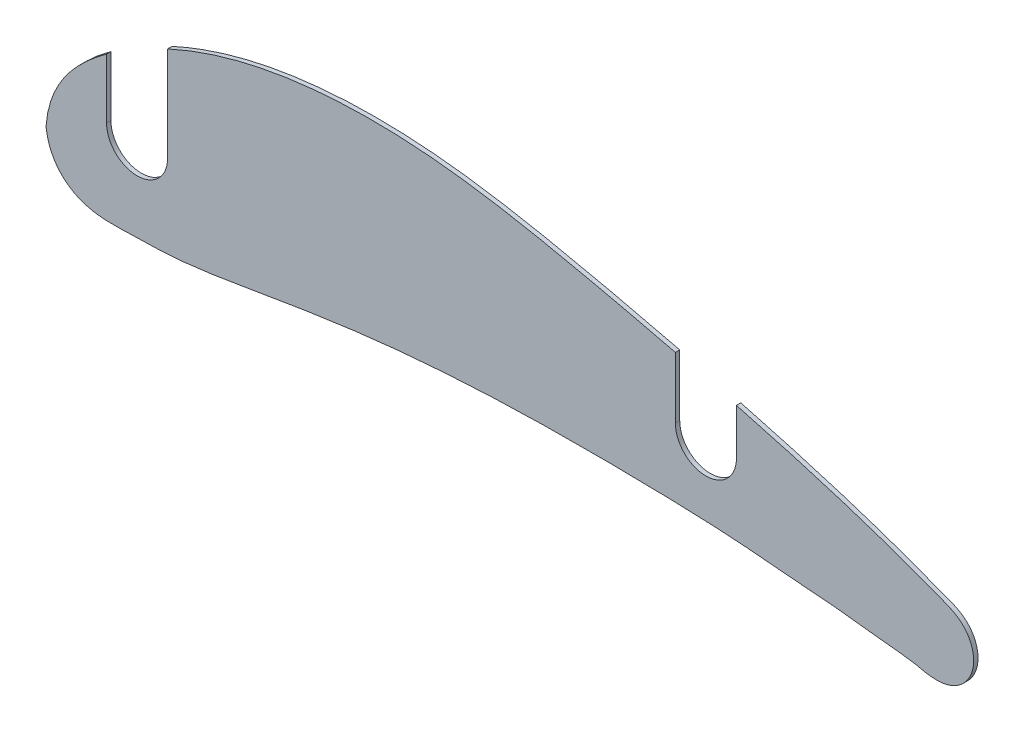
SolidWorks part; units mm, degrees
material "Balsa"
ref_plane "Front Plane" through (0, 0, 0) normal (0, 0, 1) x (1, 0, 0)
ref_plane "Top Plane" through (0, 0, 0) normal (0, 1, 0) x (1, 0, 0)
ref_plane "Right Plane" through (0, 0, 0) normal (1, 0, 0) x (0, 0, -1)
sketch "Sketch1" plane through (0, 0, 0) normal (0, 0, 1) x (1, 0, 0)
  spline S0 degree 3 poles (0.0006, 0.0001) (0.8106, 7.3592) (8.6491, 17.8566) (26.2867, 29.9752) (52.1111, 42.0692) (89.5976, 49.2908) (131.4008, 47.8848) (173.2567, 40.0411) (217.9611, 29.613) (256.9521, 19.5289) (290.3598, 8.711) (301.2732, 4.3828) (314.8169, -0.5162) (309.8463, 0.0001) knots 0 0 0 0 0.060864 0.113688 0.188609 0.312909 0.448482 0.557612 0.691544 0.852438 0.929756 0.976058 1 1 1 1
  spline S1 degree 3 poles (309.8463, 0.0001) (303.9568, 1.471) (293.9895, 2.094) (276.264, 4.5144) (260.8463, 5.4274) (235.8588, 7.8703) (205.1014, 8.8381) (157.7186, 9.0307) (110.4973, 6.1815) (66.5062, -0.5867) (36.4547, -6.0985) (15.3166, -6.1891) (1.2307, -6.9241) (0.0006, 0.0001) knots 0 0 0 0 0.057787 0.095275 0.171021 0.205339 0.335319 0.464904 0.658702 0.785512 0.893517 0.943092 1 1 1 1
extrude "Boss-Extrude1" add sketch "Sketch1" along normal blind 1.5875
sketch "Sketch2" plane through (0, 0, 1.5875) normal (0, 0, 1) x (1, 0, 0)
  circle A0 centre (20.32, 10.16) radius 6.5
  circle A1 centre (227.2963, 19.0501) radius 3
  circle A2 centre (20.32, 10.16) radius 5.75
  circle A3 centre (20.32, 10.16) radius 8
  circle A4 centre (227.2963, 19.0501) radius 4.5
  circle A5 centre (227.2963, 19.0501) radius 2.5
  dimension "D2" = 13
  dimension "D3" = 6
  dimension "D6" = 20.32
  dimension "D7" = 1.5
  dimension "D8" = 11.5
  dimension "D9" = 5
  dimension "D10" = 1.5
  dimension "D1" = 82.55
  dimension "D4" = 19.05
  dimension "D5" = 10.16
extrude "Cut-Extrude1" cut sketch "Sketch2" against normal blind 4 contours A5 | A2 region at (20.32, 10.16, 1.5875) region at (227.2963, 19.0501, 1.5875)
sketch "Sketch3" plane through (0, 0, 1.5875) normal (0, 0, 1) x (1, 0, 0)
  circle A0 centre (20.32, 10.16) radius 5.75
  circle A1 centre (227.2963, 19.0501) radius 2.5
  spline S4 degree 3 poles (-537.5821, 2953.3046) (-362.5867, 1968.3024) (-187.5913, 983.3001) (-12.5202, -2.1281) (-12.4462, -2.5545) (-12.176, -3.8198) (-11.9472, -4.6494) (-11.3848, -6.2785) (-11.0505, -7.0797) (-10.2706, -8.6419) (-9.8324, -9.3883) (-8.861, -10.8126) (-8.3277, -11.4905) (-7.4547, -12.4548) (-7.1506, -12.7683) (-6.5217, -13.3733) (-6.1984, -13.6633) (-5.2034, -14.4972) (-4.5063, -15.0051) (-3.4124, -15.698) (-3.0397, -15.9175) (-2.2783, -16.3337) (-1.8884, -16.531) (0.0848, -17.4542) (1.7227, -17.9852) (4.2479, -18.5428) (5.101, -18.6886) (6.8269, -18.9121) (7.6891, -18.9885) (10.2729, -19.1376) (11.9923, -19.129) (14.5697, -19.0646) (15.4287, -19.0354) (17.1468, -18.9865) (18.006, -18.9648) (22.3019, -18.8623) (25.7393, -18.8009) (30.8907, -18.5548) (32.6071, -18.445) (36.0379, -18.1654) (37.7526, -17.9976) (46.3222, -17.046) (53.1404, -15.9299) (63.3607, -14.1884) (66.7665, -13.5989) (73.5825, -12.4617) (76.9921, -11.9088) (87.2279, -10.3137) (94.0606, -9.3352) (107.7529, -7.6313) (114.6131, -6.9129) (128.3595, -5.7224) (135.2455, -5.2485) (149.0401, -4.5139) (155.9486, -4.2533) (166.3263, -4.0025) (169.789, -3.9425) (176.7136, -3.8642) (187.0965, -3.8094) (197.4692, -3.9166) (211.2933, -4.1577) (218.2024, -4.3251) (232.0057, -4.8961) (238.8998, -5.3016) (249.2232, -6.1931) (252.662, -6.5269) (259.5451, -7.1075) (262.9889, -7.3618) (269.8748, -7.8975) (273.3169, -8.1788) (278.4736, -8.7044) (280.1911, -8.9011) (283.6248, -9.3158) (285.3412, -9.5311) (288.7752, -9.9413) (290.493, -10.1333) (293.9309, -10.4809) (295.6507, -10.6423) (299.0876, -11.0065) (300.8047, -11.2088) (303.3742, -11.6118) (304.2297, -11.763) (305.5105, -12.0268) (305.9371, -12.1209) (335.3871, -19.1372) (362.2719, -60.0398) (582.5295, 2971.454) knots -9.029911 -9.029911 -9.029911 -9.029911 0.003906 0.003906 0.007813 0.007813 0.015625 0.015625 0.023438 0.023438 0.03125 0.03125 0.039063 0.039063 0.042969 0.042969 0.046875 0.046875 0.054688 0.054688 0.058594 0.058594 0.0625 0.0625 0.078125 0.078125 0.085938 0.085938 0.09375 0.09375 0.109375 0.109375 0.117188 0.117188 0.125 0.125 0.15625 0.15625 0.171875 0.171875 0.1875 0.1875 0.25 0.25 0.28125 0.28125 0.3125 0.3125 0.375 0.375 0.4375 0.4375 0.5 0.5 0.5625 0.5625 0.59375 0.59375 0.625 0.6875 0.6875 0.75 0.75 0.8125 0.8125 0.84375 0.84375 0.875 0.875 0.90625 0.90625 0.921875 0.921875 0.9375 0.9375 0.953125 0.953125 0.96875 0.96875 0.984375 0.984375 0.992188 0.992188 0.996094 0.996094 1.262177 1.262177 1.262177 1.262177 only from (-12.8229, -0.4244) to (307.6407, -12.5391)
  spline S5 degree 3 poles (-30.8299, -2991.3817) (252.0246, 34.8902) (278.8555, -10.0807) (309.7432, -12.7424) (310.2709, -12.7759) (311.3268, -12.8029) (311.854, -12.7961) (312.9063, -12.7287) (313.4338, -12.6676) (314.9872, -12.3972) (315.988, -12.1026) (317.4337, -11.4794) (317.9089, -11.2395) (318.8157, -10.7098) (319.6838, -10.1289) (320.4759, -9.4471) (321.2289, -8.7136) (321.5865, -8.3194) (322.5699, -7.0911) (323.1187, -6.2025) (323.7782, -4.7628) (323.9683, -4.2689) (324.2836, -3.2709) (324.4101, -2.7643) (324.6008, -1.736) (324.6652, -1.2125) (324.7285, -0.1569) (324.726, 0.8922) (324.5965, 1.9288) (324.4029, 2.9591) (324.2728, 3.4747) (323.7925, 4.9788) (323.3556, 5.9274) (322.5268, 7.2699) (322.2202, 7.7046) (321.5647, 8.5239) (321.2141, 8.9115) (320.4688, 9.6443) (320.074, 9.9894) (319.2406, 10.6374) (318.8058, 10.937) (317.4727, 11.7599) (316.5372, 12.2119) (314.6262, 13.0336) (313.6522, 13.4065) (311.697, 14.1371) (310.7161, 14.4939) (308.7579, 15.2168) (307.7794, 15.5801) (304.8459, 16.6752) (302.8934, 17.4143) (298.9854, 18.8838) (297.0281, 19.6095) (293.0959, 21.0105) (291.1228, 21.6913) (287.1674, 23.027) (285.1851, 23.6817) (279.2276, 25.616) (275.2421, 26.8663) (267.2584, 29.3011) (263.2585, 30.4844) (251.2359, 33.938) (243.1898, 36.1098) (231.0876, 39.2285) (227.0482, 40.2454) (218.9619, 42.248) (214.9155, 43.2353) (202.7668, 46.1582) (194.6542, 48.0498) (182.454, 50.7556) (178.3821, 51.6355) (170.2257, 53.3429) (166.1416, 54.1717) (157.9516, 55.7375) (151.7928, 56.8428) (145.598, 57.7968) (141.4589, 58.394) (139.384, 58.6732) (129.01, 59.9562) (120.6949, 60.6191) (108.1942, 60.9702) (104.0226, 60.98) (97.7575, 60.8192) (95.6678, 60.7364) (91.4859, 60.5096) (89.398, 60.3659) (79.0016, 59.4934) (70.7948, 58.305) (54.6421, 54.769) (46.6965, 52.4202) (37.9375, 48.979) (36.9667, 48.5856) (35.0302, 47.7767) (34.0635, 47.3607) (31.1797, 46.0826) (29.2785, 45.1906) (23.6392, 42.3949) (19.964, 40.3738) (14.5845, 37.0929) (12.8113, 35.9519) (9.3552, 33.571) (7.6711, 32.3308) (4.4084, 29.7311) (2.8297, 28.3718) (-0.2058, 25.5152) (-1.6628, 24.0183) (-3.3771, 22.0263) (-3.7146, 21.6218) (-4.3781, 20.7998) (-4.7047, 20.3815) (-5.6607, 19.1122) (-6.2653, 18.2488) (-7.9744, 15.603) (-8.9741, 13.7652) (-10.2375, 10.8836) (-10.6193, 9.9022) (-11.129, 8.3969) (-11.2886, 7.8885) (-11.5839, 6.8689) (-11.9916, 5.3328) (-12.2943, 3.7769) (-12.5275, 2.208) (-12.591, 1.6823) (-122.1238, -993.3635) (-231.5987, -1987.8827) (-341.0735, -2982.4019) knots -0.22153 -0.22153 -0.22153 -0.22153 0.003906 0.003906 0.007812 0.007812 0.011719 0.011719 0.015625 0.015625 0.023437 0.023437 0.027344 0.027344 0.03125 0.035156 0.035156 0.039062 0.039062 0.046875 0.046875 0.050781 0.050781 0.054687 0.054687 0.058594 0.058594 0.0625 0.066406 0.066406 0.070312 0.070312 0.078125 0.078125 0.082031 0.082031 0.085937 0.085937 0.089844 0.089844 0.09375 0.09375 0.101562 0.101562 0.109375 0.109375 0.117187 0.117187 0.125 0.125 0.140625 0.140625 0.15625 0.15625 0.171875 0.171875 0.1875 0.1875 0.21875 0.21875 0.25 0.25 0.3125 0.3125 0.34375 0.34375 0.375 0.375 0.4375 0.4375 0.46875 0.46875 0.5 0.5 0.53125 0.546875 0.546875 0.5625 0.5625 0.625 0.625 0.65625 0.65625 0.671875 0.671875 0.6875 0.6875 0.75 0.75 0.8125 0.8125 0.820312 0.820312 0.828125 0.828125 0.84375 0.84375 0.875 0.875 0.890625 0.890625 0.90625 0.90625 0.921875 0.921875 0.9375 0.9375 0.941406 0.941406 0.945312 0.945312 0.953125 0.953125 0.96875 0.96875 0.976562 0.976562 0.980469 0.980469 0.984375 0.992187 0.992187 0.996094 0.996094 8.372097 8.372097 8.372097 8.372097 only from (307.6407, -12.5391) to (-12.8229, -0.4244)
  spline S6 degree 3 poles (-12.8229, -0.4244) (-12.7472, -0.8503) (-12.6715, -1.2762) (-12.5202, -2.1281) (-12.4462, -2.5545) (-12.176, -3.8198) (-11.9472, -4.6494) (-11.3848, -6.2785) (-11.0505, -7.0797) (-10.2706, -8.6419) (-9.8324, -9.3883) (-8.861, -10.8126) (-8.3277, -11.4905) (-7.4547, -12.4548) (-7.1506, -12.7683) (-6.5217, -13.3733) (-6.1984, -13.6633) (-5.2034, -14.4972) (-4.5063, -15.0051) (-3.4124, -15.698) (-3.0397, -15.9175) (-2.2783, -16.3337) (-1.8884, -16.531) (0.0848, -17.4542) (1.7227, -17.9852) (4.2479, -18.5428) (5.101, -18.6886) (6.8269, -18.9121) (7.6891, -18.9885) (10.2729, -19.1376) (11.9923, -19.129) (14.5697, -19.0646) (15.4287, -19.0354) (17.1468, -18.9865) (18.006, -18.9648) (22.3019, -18.8623) (25.7393, -18.8009) (30.8907, -18.5548) (32.6071, -18.445) (36.0379, -18.1654) (37.7526, -17.9976) (46.3222, -17.046) (53.1404, -15.9299) (63.3607, -14.1884) (66.7665, -13.5989) (73.5825, -12.4617) (76.9921, -11.9088) (87.2279, -10.3137) (94.0606, -9.3352) (107.7529, -7.6313) (114.6131, -6.9129) (128.3595, -5.7224) (135.2455, -5.2485) (149.0401, -4.5139) (155.9486, -4.2533) (166.3263, -4.0025) (169.789, -3.9425) (176.7136, -3.8642) (187.0965, -3.8094) (197.4692, -3.9166) (211.2933, -4.1577) (218.2024, -4.3251) (232.0057, -4.8961) (238.8998, -5.3016) (249.2232, -6.1931) (252.662, -6.5269) (259.5451, -7.1075) (262.9889, -7.3618) (269.8748, -7.8975) (273.3169, -8.1788) (278.4736, -8.7044) (280.1911, -8.9011) (283.6248, -9.3158) (285.3412, -9.5311) (288.7752, -9.9413) (290.493, -10.1333) (293.9309, -10.4809) (295.6507, -10.6423) (299.0876, -11.0065) (300.8047, -11.2088) (303.3742, -11.6118) (304.2297, -11.763) (305.5105, -12.0268) (305.9371, -12.1209) (306.7892, -12.3239) (307.2149, -12.4328) (307.6407, -12.5391) knots 0 0 0 0 0.003906 0.003906 0.007813 0.007813 0.015625 0.015625 0.023438 0.023438 0.03125 0.03125 0.039063 0.039063 0.042969 0.042969 0.046875 0.046875 0.054688 0.054688 0.058594 0.058594 0.0625 0.0625 0.078125 0.078125 0.085938 0.085938 0.09375 0.09375 0.109375 0.109375 0.117188 0.117188 0.125 0.125 0.15625 0.15625 0.171875 0.171875 0.1875 0.1875 0.25 0.25 0.28125 0.28125 0.3125 0.3125 0.375 0.375 0.4375 0.4375 0.5 0.5 0.5625 0.5625 0.59375 0.59375 0.625 0.6875 0.6875 0.75 0.75 0.8125 0.8125 0.84375 0.84375 0.875 0.875 0.90625 0.90625 0.921875 0.921875 0.9375 0.9375 0.953125 0.953125 0.96875 0.96875 0.984375 0.984375 0.992188 0.992188 0.996094 0.996094 1 1 1 1
  spline S7 degree 3 poles (307.6407, -12.5391) (308.166, -12.5937) (308.691, -12.6517) (309.7432, -12.7424) (310.2709, -12.7759) (311.3268, -12.8029) (311.854, -12.7961) (312.9063, -12.7287) (313.4338, -12.6676) (314.9872, -12.3972) (315.988, -12.1026) (317.4337, -11.4794) (317.9089, -11.2395) (318.8157, -10.7098) (319.6838, -10.1289) (320.4759, -9.4471) (321.2289, -8.7136) (321.5865, -8.3194) (322.5699, -7.0911) (323.1187, -6.2025) (323.7782, -4.7628) (323.9683, -4.2689) (324.2836, -3.2709) (324.4101, -2.7643) (324.6008, -1.736) (324.6652, -1.2125) (324.7285, -0.1569) (324.726, 0.8922) (324.5965, 1.9288) (324.4029, 2.9591) (324.2728, 3.4747) (323.7925, 4.9788) (323.3556, 5.9274) (322.5268, 7.2699) (322.2202, 7.7046) (321.5647, 8.5239) (321.2141, 8.9115) (320.4688, 9.6443) (320.074, 9.9894) (319.2406, 10.6374) (318.8058, 10.937) (317.4727, 11.7599) (316.5372, 12.2119) (314.6262, 13.0336) (313.6522, 13.4065) (311.697, 14.1371) (310.7161, 14.4939) (308.7579, 15.2168) (307.7794, 15.5801) (304.8459, 16.6752) (302.8934, 17.4143) (298.9854, 18.8838) (297.0281, 19.6095) (293.0959, 21.0105) (291.1228, 21.6913) (287.1674, 23.027) (285.1851, 23.6817) (279.2276, 25.616) (275.2421, 26.8663) (267.2584, 29.3011) (263.2585, 30.4844) (251.2359, 33.938) (243.1898, 36.1098) (231.0876, 39.2285) (227.0482, 40.2454) (218.9619, 42.248) (214.9155, 43.2353) (202.7668, 46.1582) (194.6542, 48.0498) (182.454, 50.7556) (178.3821, 51.6355) (170.2257, 53.3429) (166.1416, 54.1717) (157.9516, 55.7375) (151.7928, 56.8428) (145.598, 57.7968) (141.4589, 58.394) (139.384, 58.6732) (129.01, 59.9562) (120.6949, 60.6191) (108.1942, 60.9702) (104.0226, 60.98) (97.7575, 60.8192) (95.6678, 60.7364) (91.4859, 60.5096) (89.398, 60.3659) (79.0016, 59.4934) (70.7948, 58.305) (54.6421, 54.769) (46.6965, 52.4202) (37.9375, 48.979) (36.9667, 48.5856) (35.0302, 47.7767) (34.0635, 47.3607) (31.1797, 46.0826) (29.2785, 45.1906) (23.6392, 42.3949) (19.964, 40.3738) (14.5845, 37.0929) (12.8113, 35.9519) (9.3552, 33.571) (7.6711, 32.3308) (4.4084, 29.7311) (2.8297, 28.3718) (-0.2058, 25.5152) (-1.6628, 24.0183) (-3.3771, 22.0263) (-3.7146, 21.6218) (-4.3781, 20.7998) (-4.7047, 20.3815) (-5.6607, 19.1122) (-6.2653, 18.2488) (-7.9744, 15.603) (-8.9741, 13.7652) (-10.2375, 10.8836) (-10.6193, 9.9022) (-11.129, 8.3969) (-11.2886, 7.8885) (-11.5839, 6.8689) (-11.9916, 5.3328) (-12.2943, 3.7769) (-12.5275, 2.208) (-12.591, 1.6823) (-12.7069, 0.629) (-12.7649, 0.1023) (-12.8229, -0.4244) knots 0 0 0 0 0.003906 0.003906 0.007812 0.007812 0.011719 0.011719 0.015625 0.015625 0.023437 0.023437 0.027344 0.027344 0.03125 0.035156 0.035156 0.039062 0.039062 0.046875 0.046875 0.050781 0.050781 0.054687 0.054687 0.058594 0.058594 0.0625 0.066406 0.066406 0.070312 0.070312 0.078125 0.078125 0.082031 0.082031 0.085937 0.085937 0.089844 0.089844 0.09375 0.09375 0.101562 0.101562 0.109375 0.109375 0.117187 0.117187 0.125 0.125 0.140625 0.140625 0.15625 0.15625 0.171875 0.171875 0.1875 0.1875 0.21875 0.21875 0.25 0.25 0.3125 0.3125 0.34375 0.34375 0.375 0.375 0.4375 0.4375 0.46875 0.46875 0.5 0.5 0.53125 0.546875 0.546875 0.5625 0.5625 0.625 0.625 0.65625 0.65625 0.671875 0.671875 0.6875 0.6875 0.75 0.75 0.8125 0.8125 0.820312 0.820312 0.828125 0.828125 0.84375 0.84375 0.875 0.875 0.890625 0.890625 0.90625 0.90625 0.921875 0.921875 0.9375 0.9375 0.941406 0.941406 0.945312 0.945312 0.953125 0.953125 0.96875 0.96875 0.976562 0.976562 0.980469 0.980469 0.984375 0.992187 0.992187 0.996094 0.996094 1 1 1 1
  dimension "D1" = 12.7
extrude "Boss-Extrude3" add sketch "Sketch3" against normal up to surface (1.5875 mm away) up to face at (224.7963, 19.0501, 0)
sketch "Sketch4" plane through (0, 0, 1.5875) normal (0, 0, 1) x (1, 0, 0)
  line L0 (9.2075, 11.7475) -> (9.2075, 65.1747)
  line L1 (31.4325, 65.1747) -> (31.4325, 11.7475)
  line L2 (9.2075, 65.1747) -> (31.4325, 65.1747)
  line L3 (216.1838, 62.4176) -> (216.1838, 20.6376)
  line L4 (238.4088, 20.6376) -> (238.4088, 62.4176)
  line L5 (238.4088, 62.4176) -> (216.1838, 62.4176)
  arc A1 (9.2075, 11.7475) -> (31.4325, 11.7475) centre (20.32, 11.7475) ccw
  arc A2 (216.1838, 20.6376) -> (238.4088, 20.6376) centre (227.2963, 20.6376) ccw
  point P4 (20.32, 65.1747)
  point P6 (20.32, 0.635)
  point P7 (20.32, 10.16)
  point P13 (227.2963, 9.5251)
  point P19 (227.2963, 19.0501)
  dimension "D1" = 22.225
  dimension "D2" = 9.525
  dimension "D3" = 64.5397
  dimension "D4" = 22.225
  dimension "D5" = 9.525
  dimension "D6" = 52.8925
extrude "Cut-Extrude2" cut sketch "Sketch4" against normal blind 2.54
